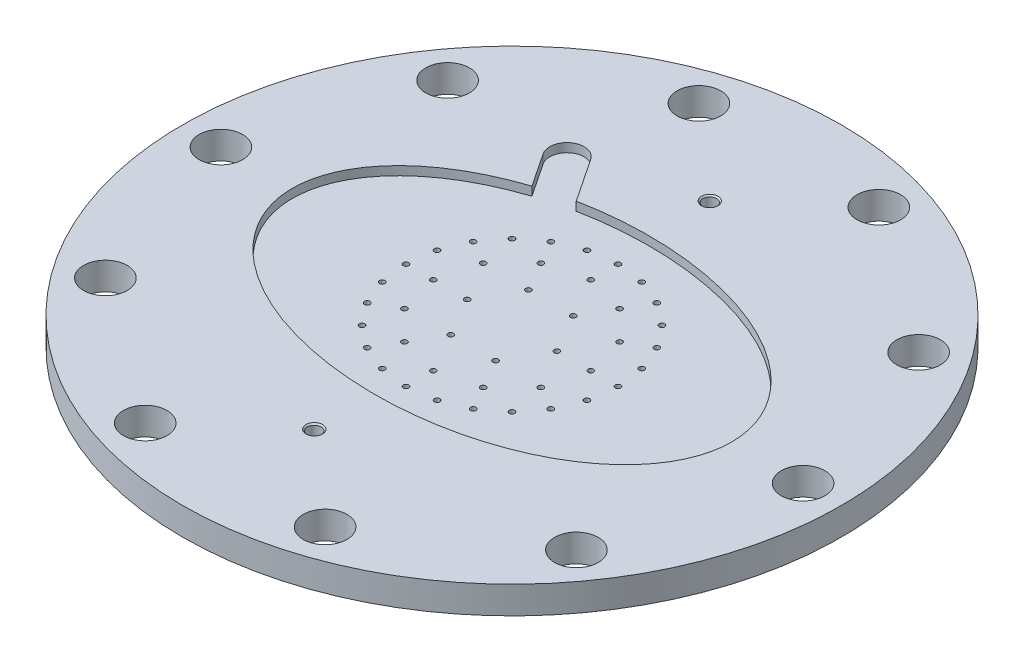
SolidWorks part; units mm, degrees
ref_plane "Front Plane" through (0, 0, 0) normal (0, 0, 1) x (1, 0, 0)
ref_plane "Top Plane" through (0, 0, 0) normal (0, 1, 0) x (1, 0, 0)
ref_plane "Right Plane" through (0, 0, 0) normal (1, 0, 0) x (0, 0, -1)
sketch "Sketch1" plane through (0, 0, 0) normal (0, 0, 1) x (1, 0, 0)
  line L0 (0, -6.35) -> (54.8259, -6.35)
  line L1 (0, 0) -> (76.2, 0)
  line L2 (0, 0) -> (0, -6.35)
  line L4 (76.2, 0) -> (76.2, -6.35)
  line L5 (54.8259, -6.35) -> (54.8259, -3.6576)
  line L6 (54.8259, -3.6576) -> (58.8899, -3.6576)
  line L7 (58.8899, -3.6576) -> (58.8899, -6.35)
  line L8 (58.8899, -6.35) -> (76.2, -6.35)
  dimension "D1" = 6.35
  dimension "D2" = 76.2
  dimension "D3" = 58.8899
  dimension "D4" = 4.064
  dimension "D5" = 2.6924
revolve "Revolve1" add sketch "Sketch1" angle 360 about L2
sketch "Sketch2" plane through (0, 0, 0) normal (0, 1, 0) x (1, 0, 0)
  line L0 (0, 0) -> (67.31, 0) construction
  dimension "D1" = 67.31
ref_axis "Axis1" through (0, 0.3175, 0) along (0, -1, 0)
hole_wizard "3/8 Clearance Hole1" positions "3DSketch2" profile "Sketch4" hole size "3/8" standard "ANSI Inch" end condition through all
sketch3d "3DSketch2"
  point P0 (67.31, 0, 0)
sketch "Sketch4" plane through (67.31, 0, 0) normal (1, 0, 0) x (0, 0, 1)
  line L0 (0, 0) -> (0, 6.35)
  line L1 (0, 6.35) -> (5.0419, 6.35)
  line L2 (5.0419, 6.35) -> (5.0419, 0)
  line L5 (5.0419, 0) -> (0, 0)
  line L11 (0, -6.35) -> (0, 107.95) construction
  dimension "Thru Hole Dia." = 10.0838
  dimension "Thru Hole Depth" = 6.35
pattern_circular "CirPattern1" count 10 over 360 about axis through (0, 0.3175, 0) along (0, -1, 0) of "3/8 Clearance Hole1"
sketch "Sketch5" plane through (0, 0, 0) normal (0, 1, 0) x (1, 0, 0)
  line L0 (-50.8, 0) -> (50.8, 0) construction
  line L1 (0, 0) -> (-25.4, 38.1) construction
  line L2 (-3.3022, -2.2015) -> (-28.7022, 35.8985)
  line L3 (3.3022, 2.2015) -> (-22.0978, 40.3015)
  arc A0 (-3.3022, -2.2015) -> (3.3022, 2.2015) centre (0, 0) ccw
  arc A1 (-22.0978, 40.3015) -> (-28.7022, 35.8985) centre (-25.4, 38.1) ccw
  ellipse E0 centre (0, 0) end of major axis (50.8, 0) minor radius 31.75
  point P10 (-12.7, 19.05)
  dimension "D5" = 3.9688
  dimension "D1" = 31.75
  dimension "D2" = 50.8
  dimension "D3" = 25.4
  dimension "D4" = 38.1
extrude "Cut-Extrude1" cut sketch "Sketch5" against normal blind 2.032 contours E0 | L3 A1 L2 A0
sketch "Sketch6" plane through (0, -2.032, 0) normal (0, 1, 0) x (1, 0, 0)
  circle A1 centre (-5.1816, -8.9748) radius 0.635
  circle A2 centre (-5.1816, -8.9748) radius 0.635
  circle A3 centre (5.1816, -8.9748) radius 0.635
  circle A4 centre (5.1816, -8.9748) radius 0.635
  circle A5 centre (24.511, 0) radius 0.635
  circle A6 centre (24.511, 0) radius 0.635
  circle A7 centre (18.2118, 0) radius 0.635
  circle A8 centre (18.2118, 0) radius 0.635
  circle A9 centre (10.3632, 0) radius 0.635
  circle A10 centre (10.3632, 0) radius 0.635
  circle A11 centre (0, -18.2118) radius 0.635
  circle A12 centre (0, -18.2118) radius 0.635
  circle A13 centre (9.1059, -15.7719) radius 0.635
  circle A14 centre (9.1059, -15.7719) radius 0.635
  circle A15 centre (15.7719, -9.1059) radius 0.635
  circle A16 centre (15.7719, -9.1059) radius 0.635
  circle A17 centre (5.1816, 8.9748) radius 0.635
  circle A18 centre (5.1816, 8.9748) radius 0.635
  circle A19 centre (-5.1816, 8.9748) radius 0.635
  circle A20 centre (-5.1816, 8.9748) radius 0.635
  circle A21 centre (-10.3632, 0) radius 0.635
  circle A22 centre (-10.3632, 0) radius 0.635
  circle A23 centre (15.7719, 9.1059) radius 0.635
  circle A24 centre (15.7719, 9.1059) radius 0.635
  circle A25 centre (9.1059, 15.7719) radius 0.635
  circle A26 centre (9.1059, 15.7719) radius 0.635
  circle A27 centre (0, 18.2118) radius 0.635
  circle A28 centre (0, 18.2118) radius 0.635
  circle A29 centre (-9.1059, 15.7719) radius 0.635
  circle A30 centre (-9.1059, 15.7719) radius 0.635
  circle A31 centre (-15.7719, 9.1059) radius 0.635
  circle A32 centre (-15.7719, 9.1059) radius 0.635
  circle A33 centre (-18.2118, 0) radius 0.635
  circle A34 centre (-18.2118, 0) radius 0.635
  circle A35 centre (-15.7719, -9.1059) radius 0.635
  circle A36 centre (-15.7719, -9.1059) radius 0.635
  circle A37 centre (-9.1059, -15.7719) radius 0.635
  circle A38 centre (-9.1059, -15.7719) radius 0.635
  circle A39 centre (-6.3439, -23.6758) radius 0.635
  circle A40 centre (-6.3439, -23.6758) radius 0.635
  circle A41 centre (0, -24.511) radius 0.635
  circle A42 centre (0, -24.511) radius 0.635
  circle A43 centre (6.3439, -23.6758) radius 0.635
  circle A44 centre (6.3439, -23.6758) radius 0.635
  circle A45 centre (12.2555, -21.2271) radius 0.635
  circle A46 centre (12.2555, -21.2271) radius 0.635
  circle A47 centre (17.3319, -17.3319) radius 0.635
  circle A48 centre (17.3319, -17.3319) radius 0.635
  circle A49 centre (21.2271, -12.2555) radius 0.635
  circle A50 centre (21.2271, -12.2555) radius 0.635
  circle A51 centre (23.6758, -6.3439) radius 0.635
  circle A52 centre (23.6758, -6.3439) radius 0.635
  circle A53 centre (-17.3319, 17.3319) radius 0.635
  circle A54 centre (-17.3319, 17.3319) radius 0.635
  circle A55 centre (-21.2271, 12.2555) radius 0.635
  circle A56 centre (-21.2271, 12.2555) radius 0.635
  circle A57 centre (-23.6758, 6.3439) radius 0.635
  circle A58 centre (-23.6758, 6.3439) radius 0.635
  circle A59 centre (-24.511, 0) radius 0.635
  circle A60 centre (-24.511, 0) radius 0.635
  circle A61 centre (-23.6758, -6.3439) radius 0.635
  circle A62 centre (-23.6758, -6.3439) radius 0.635
  circle A63 centre (-21.2271, -12.2555) radius 0.635
  circle A64 centre (-21.2271, -12.2555) radius 0.635
  circle A65 centre (-17.3319, -17.3319) radius 0.635
  circle A66 centre (-17.3319, -17.3319) radius 0.635
  circle A67 centre (-12.2555, -21.2271) radius 0.635
  circle A68 centre (-12.2555, -21.2271) radius 0.635
  circle A69 centre (23.6758, 6.3439) radius 0.635
  circle A70 centre (23.6758, 6.3439) radius 0.635
  circle A71 centre (21.2271, 12.2555) radius 0.635
  circle A72 centre (21.2271, 12.2555) radius 0.635
  circle A73 centre (17.3319, 17.3319) radius 0.635
  circle A74 centre (17.3319, 17.3319) radius 0.635
  circle A75 centre (12.2555, 21.2271) radius 0.635
  circle A76 centre (12.2555, 21.2271) radius 0.635
  circle A77 centre (6.3439, 23.6758) radius 0.635
  circle A78 centre (6.3439, 23.6758) radius 0.635
  circle A79 centre (0, 24.511) radius 0.635
  circle A80 centre (0, 24.511) radius 0.635
  circle A81 centre (-6.3439, 23.6758) radius 0.635
  circle A82 centre (-6.3439, 23.6758) radius 0.635
  circle A83 centre (-12.2555, 21.2271) radius 0.635
  circle A84 centre (-12.2555, 21.2271) radius 0.635
  dimension "D1" = 0
  dimension "D2" = 0
  dimension "D3" = 0
  dimension "D4" = 0
  dimension "D5" = 0
  dimension "D6" = 0
  dimension "D7" = 0
  dimension "D8" = 0
  dimension "D9" = 0
  dimension "D10" = 0
  dimension "D11" = 0
  dimension "D12" = 0
  dimension "D13" = 0
  dimension "D14" = 0
  dimension "D15" = 0
  dimension "D16" = 0
  dimension "D17" = 0
  dimension "D18" = 0
  dimension "D19" = 0
  dimension "D20" = 0
  dimension "D21" = 0
  dimension "D22" = 0
  dimension "D23" = 0
  dimension "D24" = 0
  dimension "D25" = 0
  dimension "D26" = 0
  dimension "D27" = 0
  dimension "D28" = 0
  dimension "D29" = 0
  dimension "D30" = 0
  dimension "D31" = 0
  dimension "D32" = 0
  dimension "D33" = 0
  dimension "D34" = 0
  dimension "D35" = 0
  dimension "D36" = 0
  dimension "D37" = 0
  dimension "D38" = 0
  dimension "D39" = 0
  dimension "D40" = 0
  dimension "D41" = 0
  dimension "D42" = 0
extrude "Cut-Extrude2" cut sketch "Sketch6" against normal through all
hole_wizard "1/8 (0.125) Diameter Hole1" positions "3DSketch3" profile "Sketch7" hole size "1/8" standard "ANSI Inch"
sketch3d "3DSketch3"
  line L0 (0, 0, 45.72) -> (0, 0, -45.72) construction
  point P15 (0, 0, 45.72)
  point P21 (0, 0, -45.72)
  dimension "D1" = 91.44
sketch "Sketch7" plane through (0, 0, -45.72) normal (1, 0, 0) x (0, 0, 1)
  line L0 (0, 0) -> (0, 3.81)
  line L1 (0, 3.81) -> (1.5875, 2.8561)
  line L2 (1.5875, 2.8561) -> (1.5875, 0.3175)
  line L3 (1.5875, 0.3175) -> (1.905, 0)
  line L5 (1.905, 0) -> (0, 0)
  line L6 (-1.5875, 0.3175) -> (-1.905, 0) construction
  line L10 (0, 3.81) -> (-1.5875, 2.8561) construction
  line L11 (0, -6.35) -> (0, 107.95) construction
  dimension "Hole Dia." = 3.175
  dimension "Hole Depth" = 3.81
  dimension "Near C'Sink Dia." = 3.81
  dimension "Near C'Sink Angle" = 90
  dimension "Drill Angle" = 118
